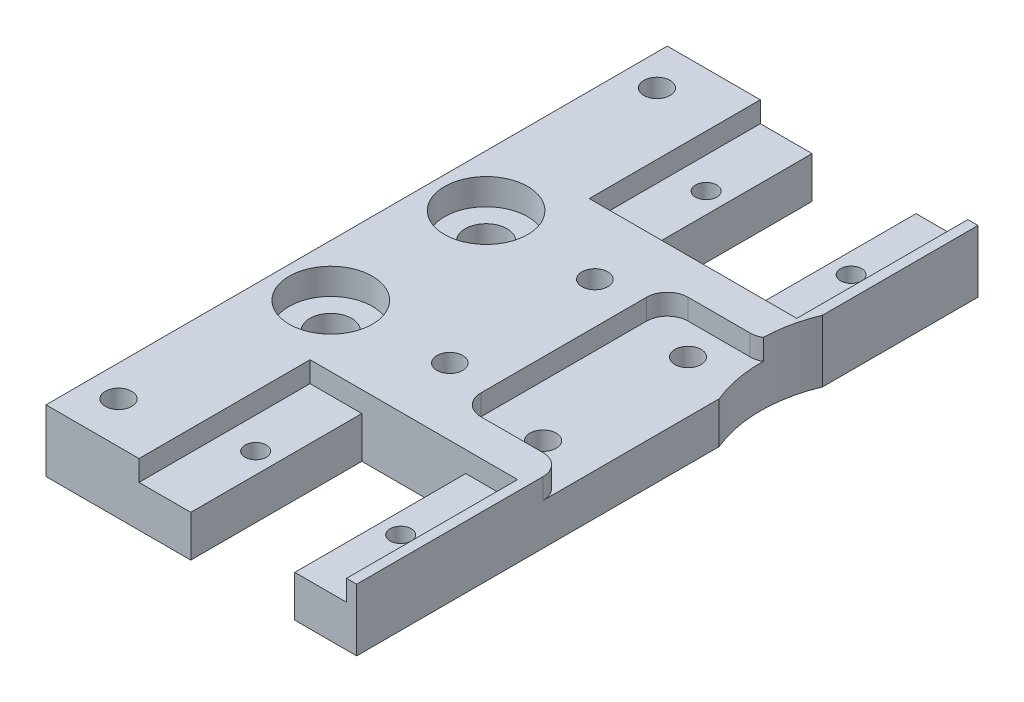
SolidWorks part; units mm, degrees
ref_plane "前视基准面" through (0, 0, 0) normal (0, 0, 1) x (1, 0, 0)
ref_plane "上视基准面" through (0, 0, 0) normal (0, 1, 0) x (1, 0, 0)
ref_plane "右视基准面" through (0, 0, 0) normal (1, 0, 0) x (0, 0, -1)
sketch "草图1" plane through (0, 0, 0) normal (0, 1, 0) x (1, 0, 0)
  line L0 (-160.9101, 0) -> (0, 0) construction
  line L3 (43, 1.5) -> (58.4568, 3.5349)
  line L4 (0, 15) -> (10, 30)
  line L5 (59.9953, -9.8805) -> (31, -30)
  line L6 (10, 30) -> (31, 30)
  line L7 (0, -15) -> (10, -30)
  line L8 (43, -1.5) -> (58.4568, -3.5349)
  line L9 (43, 1.5) -> (40, 1.5)
  line L11 (40, 1.5) -> (40, -1.5)
  line L12 (0, 15) -> (0, -15)
  line L13 (40, -1.5) -> (43, -1.5)
  line L14 (36.676, 0) -> (71.1357, 0) construction
  line L15 (59.9953, 9.8805) -> (31, 30)
  line L16 (10, -30) -> (31, -30)
  arc A3 (58.4568, 3.5349) -> (59.9953, 9.8805) centre (58, 7.005) ccw
  arc A4 (58.4568, -3.5349) -> (59.9953, -9.8805) centre (58, -7.005) cw
  point P33 (40, 0)
  dimension "D2" = 3
  dimension "D3" = 3.5
  dimension "D5" = 7.5
  dimension "D6" = 15
  dimension "D7" = 10
  dimension "D8" = 40
  dimension "D10" = 60
  dimension "D11" = 21
  dimension "D12" = 21
  dimension "D1" = 3
  dimension "D4" = 3
  dimension "D9" = 30
extrude "凸台-拉伸1" add sketch "草图1" along normal blind 2
sketch "草图2" plane through (0, 0, 0) normal (0, -1, 0) x (1, 0, 0)
  line L0 (15, 37.5) -> (15, -37.5)
  line L1 (10, -30) -> (0, -15) construction
  line L12 (10, 30) -> (0, 15)
  line L13 (0, 15) -> (0, -15)
  line L14 (0, -15) -> (10, -30)
  line L15 (31, -30) -> (59.9953, -9.8805)
  line L16 (58.4568, -3.5349) -> (43, -1.5)
  line L17 (43, -1.5) -> (40, -1.5)
  line L18 (40, -1.5) -> (40, 1.5)
  line L19 (40, 1.5) -> (43, 1.5)
  line L20 (43, 1.5) -> (58.4568, 3.5349)
  line L21 (59.9953, 9.8805) -> (31, 30)
  line L22 (10, 30) -> (0, 15)
  line L23 (0, 15) -> (0, -15)
  line L24 (0, -15) -> (10, -30)
  line L25 (31, -30) -> (59.9953, -9.8805)
  line L26 (58.4568, -3.5349) -> (43, -1.5)
  line L27 (43, -1.5) -> (40, -1.5)
  line L28 (40, -1.5) -> (40, 1.5)
  line L29 (40, 1.5) -> (43, 1.5)
  line L30 (43, 1.5) -> (58.4568, 3.5349)
  line L31 (59.9953, 9.8805) -> (31, 30)
  line L34 (31, 30) -> (10, 30)
  line L35 (31, 30) -> (10, 30)
  line L36 (10, -30) -> (31, -30)
  line L37 (10, -30) -> (31, -30)
  arc A6 (59.9953, -9.8805) -> (58.4568, -3.5349) centre (58, -7.005) ccw
  arc A7 (58.4568, 3.5349) -> (59.9953, 9.8805) centre (58, 7.005) ccw
  arc A10 (59.9953, -9.8805) -> (58.4568, -3.5349) centre (58, -7.005) ccw
  arc A11 (58.4568, 3.5349) -> (59.9953, 9.8805) centre (58, 7.005) ccw
  line M17 (10, 30) -> (0, 15)
  line M18 (0, 15) -> (0, -15)
  line M19 (0, -15) -> (10, -30)
  dimension "D2" = 15
  dimension "D1" = 0
extrude "凸台-拉伸2" add sketch "草图2" along normal blind 3 contours L0 M17 M18 M19 region at (8.3333, 0, 0)
sketch "草图3" plane through (0, 0, 0) normal (0, -1, 0) x (1, 0, 0)
  line L3 (31, -30) -> (31, 30)
  line L10 (15, 30) -> (15, -30)
  line L11 (31, -30) -> (59.9953, -9.8805)
  line L12 (58.4568, -3.5349) -> (43, -1.5)
  line L13 (43, -1.5) -> (40, -1.5)
  line L14 (40, -1.5) -> (40, 1.5)
  line L15 (40, 1.5) -> (43, 1.5)
  line L16 (43, 1.5) -> (58.4568, 3.5349)
  line L17 (59.9953, 9.8805) -> (31, 30)
  line L18 (15, 30) -> (15, -30)
  line L28 (31, 30) -> (15, 30)
  line L29 (31, 30) -> (15, 30)
  line L30 (15, -30) -> (31, -30)
  line L31 (15, -30) -> (31, -30)
  arc A7 (59.9953, -9.8805) -> (58.4568, -3.5349) centre (58, -7.005) ccw
  arc A8 (58.4568, 3.5349) -> (59.9953, 9.8805) centre (58, 7.005) ccw
  dimension "D2" = 0
extrude "凸台-拉伸3" add sketch "草图3" along normal blind 3
sketch "草图4" plane through (0, 2, 0) normal (0, 1, 0) x (1, 0, 0)
  line L0 (0, 0) -> (40, 0) construction
  line L1 (40, -1.5) -> (40, 1.5) construction
  line L2 (31, 30) -> (10, 30) construction
  line L7 (15, -30) -> (25, -30)
  line L8 (10, -30) -> (31, -30) construction
  line L9 (25, -30) -> (25, -13.5)
  line L10 (25, -13.5) -> (15, -13.5)
  line L11 (15, -13.5) -> (15, -30)
  line L12 (31, 30) -> (10, 30) construction
  line L13 (25, 13.5) -> (15, 13.5)
  line L14 (25, 30) -> (25, 13.5)
  line L15 (15, 30) -> (25, 30)
  line L16 (15, 13.5) -> (15, 30)
  point P14 (20.5, -30)
  point P17 (20.5, 30)
  dimension "D1" = 10
  dimension "D2" = 16.5
  dimension "D3" = 5
sketch "草图5" plane through (0, -3, 0) normal (0, -1, 0) x (1, 0, 0)
  line L6 (10, -30) -> (31, -30)
  line L7 (31, -30) -> (31, 30)
  line L8 (31, 30) -> (10, 30)
  line L9 (10, 30) -> (0, 15)
  line L10 (0, 15) -> (0, -15)
  line L11 (0, -15) -> (10, -30)
  line L12 (10, -30) -> (31, -30)
  line L13 (31, -30) -> (31, 30)
  line L14 (31, 30) -> (10, 30)
  line L15 (10, 30) -> (0, 15)
  line L16 (0, 15) -> (0, -15)
  line L17 (0, -15) -> (10, -30)
  dimension "D1" = 0
extrude "切除-拉伸1" cut sketch "草图5" against normal blind 1
extrude "切除-拉伸2" cut sketch "草图4" against normal through all
sketch "草图6" plane through (0, 2, 0) normal (0, 1, 0) x (1, 0, 0)
  line L1 (10, 30) -> (30, 30)
  line L2 (10, 30) -> (10, 13.5)
  line L3 (10, 13.5) -> (30, 13.5)
  line L4 (30, 30) -> (30, 13.5)
  line L5 (10, -30) -> (30, -30)
  line L6 (10, -30) -> (10, -13.5)
  line L7 (10, -13.5) -> (30, -13.5)
  line L8 (30, -30) -> (30, -13.5)
  dimension "D1" = 16.5
  dimension "D2" = 20
  dimension "D3" = 20
  dimension "D4" = 16.5
extrude "切除-拉伸4" cut sketch "草图6" against normal blind 2
sketch "草图7" plane through (0, 2, 0) normal (0, 1, 0) x (1, 0, 0)
  line L1 (40, 1.5) -> (43, 1.5) construction
  line L2 (43, -1.5) -> (40, -1.5) construction
  line L3 (0, 15) -> (0, -15) construction
  circle A0 centre (58, 7.005) radius 1
  circle A1 centre (58, -7.005) radius 1
  circle A2 centre (43, -6) radius 1
  circle A3 centre (43, 6) radius 1
  circle A4 centre (6, 7.5) radius 4
  circle A5 centre (6, -7.5) radius 4
  dimension "D1" = 2
  dimension "D2" = 2
  dimension "D3" = 2
  dimension "D4" = 2
  dimension "D5" = 4.5
  dimension "D6" = 4.5
  dimension "D7" = 8
  dimension "D8" = 8
  dimension "D9" = 6
  dimension "D10" = 6
  dimension "D11" = 6
  dimension "D12" = 6
extrude "切除-拉伸5" cut sketch "草图7" against normal blind 3.5
sketch "草图10" plane through (0, 0, 0) normal (0, -1, 0) x (1, 0, 0)
  circle A0 centre (43, 6) radius 4
  dimension "D1" = 8
extrude "凸台-拉伸5" add sketch "草图10" along normal blind 2
sketch "草图11" plane through (0, 2, 0) normal (0, 1, 0) x (1, 0, 0)
  circle A0 centre (43, -6) radius 3
  dimension "D1" = 6
extrude "切除-拉伸6" cut sketch "草图11" against normal blind 2.5
sketch "草图12" plane through (0, -0.5, 0) normal (0, 1, 0) x (1, 0, 0)
  circle A0 centre (43, -6) radius 1.75
  dimension "D1" = 3.5
extrude "切除-拉伸7" cut sketch "草图12" against normal blind 2.5
sketch "草图14" plane through (0, 2, 0) normal (0, 1, 0) x (1, 0, 0)
  circle A0 centre (6, 7.5) radius 1.5
  circle A1 centre (6, -7.5) radius 1.5
  dimension "D1" = 3
  dimension "D2" = 3
extrude "切除-拉伸8" cut sketch "草图14" against normal through all
sketch "草图15" plane through (0, 0, 0) normal (0, 1, 0) x (1, 0, 0)
  line L0 (15, 13.5) -> (15, 30) construction
  line L1 (25, 30) -> (25, 13.5) construction
  line L2 (25, -30) -> (25, -13.5) construction
  line L3 (15, -13.5) -> (15, -30) construction
  line L4 (10, -30) -> (15, -30) construction
  line L5 (25, -30) -> (30, -30) construction
  line L6 (30, 30) -> (25, 30) construction
  line L7 (15, 30) -> (10, 30) construction
  circle A0 centre (13, 21.75) radius 1.25
  circle A1 centre (27, 21.75) radius 1.25
  circle A2 centre (27, -21.75) radius 1.25
  circle A3 centre (13, -21.75) radius 1.25
  dimension "D1" = 2
  dimension "D2" = 2
  dimension "D3" = 2
  dimension "D4" = 2
  dimension "D5" = 2.5
  dimension "D6" = 2.5
  dimension "D7" = 2.5
  dimension "D8" = 2.5
  dimension "D9" = 8.25
  dimension "D10" = 8.25
  dimension "D11" = 8.25
  dimension "D12" = 8.25
extrude "切除-拉伸9" cut sketch "草图15" against normal blind 10
sketch "草图16" plane through (0, 2, 0) normal (0, 1, 0) x (1, 0, 0)
  line L0 (40, 0) -> (0, 0)
  line L1 (40, -1.5) -> (40, 1.5) construction
  circle A0 centre (17, 7) radius 1.25
  circle A1 centre (17, -7) radius 1.25
  circle A2 centre (37, 16) radius 1.25
  circle A3 centre (37, -16) radius 1.25
  dimension "D1" = 2.5
  dimension "D2" = 2.5
  dimension "D3" = 7
  dimension "D4" = 7
  dimension "D5" = 23
  dimension "D6" = 23
  dimension "D7" = 2.5
  dimension "D8" = 2.5
  dimension "D9" = 16
  dimension "D10" = 3
  dimension "D11" = 16
  dimension "D12" = 3
extrude "切除-拉伸10" cut sketch "草图16" against normal blind 10 contours A1 | A0 | A2 | A3 region at (17, 2, -7) region at (17, 2, 7) region at (37, 2, -16) region at (37, 2, 16)
sketch "草图17" plane through (0, -1.5, 0) normal (0, 1, 0) x (1, 0, 0)
  circle A0 centre (6, 7.5) radius 4.5
  circle A1 centre (6, -7.5) radius 4.5
  circle A2 centre (6, 12) radius 0.8
  dimension "D1" = 9
  dimension "D2" = 9
  dimension "D3" = 1.6
sketch "草图18" plane through (0, -2, 0) normal (0, -1, 0) x (1, 0, 0)
  line L0 (0, 15) -> (10.5, 15)
  line L1 (10.5, 15) -> (10.5, -15)
  line L2 (10.5, -15) -> (0, -15)
  line L3 (0, 15) -> (0, -15) construction
  line L4 (0, -15) -> (0, 15)
  circle A0 centre (6, -7.5) radius 4.5 construction
  circle A1 centre (6, 7.5) radius 1.5 construction
  circle A2 centre (6, 7.5) radius 1.5
  circle A3 centre (6, -7.5) radius 1.5 construction
  circle A4 centre (6, -7.5) radius 1.5
extrude "凸台-拉伸6" add sketch "草图18" along normal blind 2
sketch "草图19" plane through (0, 2, 0) normal (0, 1, 0) x (1, 0, 0)
  circle A0 centre (6, 12) radius 1.75
  circle A1 centre (6, 3) radius 1.75
  circle A2 centre (6, 7.5) radius 4.5 construction
  dimension "D1" = 3.5
  dimension "D2" = 3.5
extrude "切除-拉伸11" cut sketch "草图19" against normal offset from surface (5 mm away) 1 up to face at (5.25, -4, 0)
sketch "草图20" plane through (0, -3, 0) normal (0, 1, 0) x (1, 0, 0)
  circle A0 centre (6, 12) radius 0.9
  circle A1 centre (6, 3) radius 0.9
  dimension "D1" = 1.8
  dimension "D2" = 1.8
extrude "切除-拉伸12" cut sketch "草图20" against normal through all
sketch "草图22" plane through (0, 2, 0) normal (0, 1, 0) x (1, 0, 0)
  circle A0 centre (6, -3) radius 1.75
  circle A1 centre (6, -7.5) radius 4.5 construction
  circle A2 centre (6, -12) radius 1.75
  dimension "D1" = 3.5
  dimension "D2" = 3.5
extrude "切除-拉伸13" cut sketch "草图22" against normal offset from surface (5 mm away) 1 up to face at (6, -4, -11.1)
sketch "草图23" plane through (0, -3, 0) normal (0, 1, 0) x (1, 0, 0)
  circle A0 centre (6, -3) radius 0.9
  circle A1 centre (6, -12) radius 0.9
  dimension "D1" = 1.8
  dimension "D2" = 1.8
extrude "切除-拉伸14" cut sketch "草图23" against normal through all
fillet "圆角1" radius 2 1 edges at (10.5, -3, 15)
fillet "圆角2" radius 2 1 edges at (10.5, -3, -15)
sketch "草图24" plane through (0, 2, 0) normal (0, 1, 0) x (1, 0, 0)
  line L0 (10, 30) -> (0, 30)
  line L1 (0, 30) -> (0, 15)
  line L2 (0, 15) -> (10, 30)
  line L3 (0, -15) -> (0, -30)
  line L4 (0, -30) -> (10, -30)
  line L5 (10, -30) -> (0, -15)
extrude "凸台-拉伸7" add sketch "草图24" against normal up to surface (4 mm away) up to face at (13, -2, -20.5)
sketch "草图25" plane through (0, 2, 0) normal (0, 1, 0) x (1, 0, 0)
  line L0 (0, 30) -> (0, -30) construction
  line L1 (10, 30) -> (0, 30) construction
  line L2 (0, -30) -> (10, -30) construction
  circle A0 centre (4, 26) radius 1.25
  circle A1 centre (4, -26) radius 1.25
  dimension "D1" = 4
  dimension "D2" = 4
  dimension "D3" = 4
  dimension "D4" = 2.5
  dimension "D5" = 4
  dimension "D6" = 2.5
extrude "切除-拉伸15" cut sketch "草图25" against normal blind 10
sketch "草图26" plane through (0, 2, 0) normal (0, 1, 0) x (1, 0, 0)
  line L21 (9.98, 30) -> (30.02, 30)
  line L24 (30.02, 13.48) -> (30.02, 30)
  line L25 (9.98, 13.48) -> (30.02, 13.48)
  line L26 (9.98, 30) -> (9.98, 13.48)
  line L27 (30.02, 13.48) -> (30.02, 30)
  line L28 (9.98, 13.48) -> (30.02, 13.48)
  line L29 (9.98, 30) -> (9.98, 13.48)
  line L34 (9.98, -30) -> (30.02, -30)
  line L37 (30.02, -30) -> (30.02, -13.48)
  line L38 (30.02, -13.48) -> (9.98, -13.48)
  line L39 (9.98, -13.48) -> (9.98, -30)
  line L40 (30.02, -30) -> (30.02, -13.48)
  line L41 (30.02, -13.48) -> (9.98, -13.48)
  line L42 (9.98, -13.48) -> (9.98, -30)
  dimension "D1" = 0.02
  dimension "D2" = 0.02
extrude "切除-拉伸16" cut sketch "草图26" against normal up to surface (2 mm away) up to face at (27, 0, 23)
sketch "草图27" plane through (0, 0, 0) normal (0, 1, 0) x (1, 0, 0)
  line L0 (9.98, 13.48) -> (30.02, 13.48) construction
  line L1 (14.98, 13.48) -> (25.02, 13.48)
  line L2 (30.02, -13.48) -> (9.98, -13.48) construction
  line L3 (25.02, -13.48) -> (14.98, -13.48)
  line L9 (14.98, -13.5) -> (14.98, -30)
  line L10 (14.98, -13.48) -> (14.98, -30)
  line L11 (14.98, -30) -> (25.02, -30)
  line L12 (25.02, -30) -> (25.02, -13.5)
  line L13 (25.02, -30) -> (25.02, -13.48)
  line L18 (14.98, 13.5) -> (14.98, 30)
  line L19 (14.98, 13.48) -> (14.98, 30)
  line L20 (14.98, 30) -> (25.02, 30)
  line L21 (25.02, 30) -> (25.02, 13.5)
  line L22 (25.02, 30) -> (25.02, 13.48)
  dimension "D1" = 0.02
  dimension "D2" = 0.02
  dimension "D4" = 0.02
  dimension "D5" = 0.02
extrude "切除-拉伸17" cut sketch "草图27" against normal up to surface (2 mm away) up to face at (4, -2, -24.75)
sketch "草图28" plane through (0, 2, 0) normal (0, 1, 0) x (1, 0, 0)
  circle A5 centre (43, 6) radius 1.02
  circle A6 centre (43, 6) radius 1.02
  circle A13 centre (58, 7.005) radius 1.02
  circle A14 centre (58, 7.005) radius 1.02
  circle A16 centre (58, -7.005) radius 1.02
  circle A17 centre (58, -7.005) radius 1.02
  circle A19 centre (6, 12) radius 0.92
  circle A20 centre (6, 12) radius 0.92
  circle A22 centre (6, 3) radius 0.92
  circle A23 centre (6, 3) radius 0.92
  circle A25 centre (6, -3) radius 0.92
  circle A26 centre (6, -3) radius 0.92
  circle A28 centre (6, -12) radius 0.92
  circle A29 centre (6, -12) radius 0.92
  circle A31 centre (4, 26) radius 1.27
  circle A32 centre (4, 26) radius 1.27
  circle A34 centre (4, -26) radius 1.27
  circle A35 centre (4, -26) radius 1.27
  dimension "D1" = 0.02
  dimension "D2" = 0.02
  dimension "D3" = 0.02
  dimension "D4" = 0.02
  dimension "D5" = 0.02
  dimension "D6" = 0.02
  dimension "D7" = 0.02
  dimension "D8" = 0.02
  dimension "D9" = 0.02
extrude "切除-拉伸18" cut sketch "草图28" against normal through all both and the other way through all
sketch "草图29" plane through (0, 0, 0) normal (0, 1, 0) x (1, 0, 0)
  point P0 (13, 21.75)
  point P1 (27, 21.75)
  point P3 (27, -21.75)
  point P5 (13, -21.75)
sketch "草图30" plane through (0, 0, 0) normal (0, 1, 0) x (1, 0, 0)
  circle A0 centre (13, 21.75) radius 1.5751
  circle A1 centre (27, 21.75) radius 1.9311
  circle A2 centre (27, -21.75) radius 1.7161
  circle A3 centre (13, -21.75) radius 1.8166
extrude "凸台-拉伸8" add sketch "草图30" against normal up to surface (2 mm away) up to face at (4, -2, 27.27)
hole_wizard "M2.5 螺纹孔1" positions "草图31" profile "草图32" tap size "M2.5" standard "GB" end condition through all
sketch "草图31" plane through (0, 0, 0) normal (0, 1, 0) x (1, 0, 0)
  point P0 (13, 21.75)
  point P3 (27, 21.75)
  point P6 (27, -21.75)
  point P9 (13, -21.75)
sketch "草图32" plane through (13, 0, -21.75) normal (1, 0, 0) x (0, 0, 1)
  line L0 (0, 0) -> (0, 4)
  line L1 (0, 4) -> (1.025, 4)
  line L2 (1.025, 4) -> (1.025, 0)
  line L5 (1.025, 0) -> (0, 0)
  line L11 (0, -6.35) -> (0, 107.95) construction
  dimension "通孔螺纹孔钻头直径" = 2.05
  dimension "通孔螺纹孔钻头深度" = 4
sketch "草图33" plane through (0, 2, 0) normal (0, 1, 0) x (1, 0, 0)
  circle A0 centre (43, -6) radius 3.02
  circle A1 centre (43, -6) radius 3 construction
  dimension "D1" = 0.02
extrude "切除-拉伸19" cut sketch "草图33" against normal blind 2.53
sketch "草图35" plane through (0, -1.5, 0) normal (0, 1, 0) x (1, 0, 0)
  circle A0 centre (6, 7.5) radius 1.5 construction
  circle A1 centre (6, 7.5) radius 1.5
  circle A2 centre (6, -7.5) radius 1.5 construction
  circle A3 centre (6, -7.5) radius 1.5
  arc A4 (4.4501, -3.8125) -> (7.5499, -3.8125) centre (6, -3) ccw
  arc A5 (4.4501, -3.8125) -> (4.4501, -11.1875) centre (6, -7.5) ccw
  arc A6 (7.5499, -11.1875) -> (4.4501, -11.1875) centre (6, -12) ccw
  arc A7 (7.5499, -11.1875) -> (7.5499, -3.8125) centre (6, -7.5) ccw
  arc A8 (4.4501, -3.8125) -> (7.5499, -3.8125) centre (6, -3) ccw
  arc A9 (4.4501, -3.8125) -> (4.4501, -11.1875) centre (6, -7.5) ccw
  arc A10 (7.5499, -11.1875) -> (4.4501, -11.1875) centre (6, -12) ccw
  arc A11 (7.5499, -11.1875) -> (7.5499, -3.8125) centre (6, -7.5) ccw
  arc A12 (4.4501, 11.1875) -> (7.5499, 11.1875) centre (6, 12) ccw
  arc A13 (4.4501, 11.1875) -> (4.4501, 3.8125) centre (6, 7.5) ccw
  arc A14 (7.5499, 3.8125) -> (4.4501, 3.8125) centre (6, 3) ccw
  arc A15 (7.5499, 3.8125) -> (7.5499, 11.1875) centre (6, 7.5) ccw
  arc A16 (4.4501, 11.1875) -> (7.5499, 11.1875) centre (6, 12) ccw
  arc A17 (4.4501, 11.1875) -> (4.4501, 3.8125) centre (6, 7.5) ccw
  arc A18 (7.5499, 3.8125) -> (4.4501, 3.8125) centre (6, 3) ccw
  arc A19 (7.5499, 3.8125) -> (7.5499, 11.1875) centre (6, 7.5) ccw
  arc M9 (7.5499, -3.8125) -> (4.4501, -3.8125) centre (6, -3) cw
  arc M10 (4.4501, -3.8125) -> (4.4501, -11.1875) centre (6, -7.5) ccw
  arc M11 (4.4501, -11.1875) -> (7.5499, -11.1875) centre (6, -12) cw
  arc M12 (7.5499, -11.1875) -> (7.5499, -3.8125) centre (6, -7.5) ccw
  circle M13 centre (6, -7.5) radius 1.5
  dimension "D1" = 0
  dimension "D2" = 0
extrude "凸台-拉伸9" add sketch "草图35" along normal up to surface (3.5 mm away) contours A18 A19 A16 A17 A1 | M12 M9 M10 M11 M13 region at (6, -1.5, 4.8588) region at (6, -1.5, -10.1412) up to face at (43, 2, 9.02)
sketch "草图36" plane through (0, 2, 0) normal (0, 1, 0) x (1, 0, 0)
  circle A0 centre (6, 7.5) radius 4.02
  circle A1 centre (6, -7.5) radius 4.02
  dimension "D1" = 8.04
  dimension "D2" = 8.04
extrude "切除-拉伸21" cut sketch "草图36" against normal blind 2.53
sketch "草图37" plane through (0, -3, 0) normal (0, 1, 0) x (1, 0, 0)
  circle A0 centre (6, -12) radius 0.92 construction
  circle A1 centre (6, 12) radius 1.75
  circle A2 centre (6, 12) radius 1.75
  circle A3 centre (6, 3) radius 1.75
  circle A4 centre (6, 3) radius 1.75
  circle A5 centre (6, -3) radius 1.75
  circle A6 centre (6, -3) radius 1.75
  circle A7 centre (6, -12) radius 1.75
  circle A8 centre (6, -12) radius 1.75
  circle A9 centre (6, -12) radius 0.92
  circle A10 centre (6, -3) radius 0.92 construction
  circle A11 centre (6, -3) radius 0.92
  circle A12 centre (6, 3) radius 0.92 construction
  circle A13 centre (6, 3) radius 0.92
  circle A14 centre (6, 12) radius 0.92 construction
  circle A15 centre (6, 12) radius 0.92
  circle M6 centre (6, 12) radius 0.92
  circle M7 centre (6, 12) radius 1.75
  dimension "D1" = 0
  dimension "D2" = 0
  dimension "D3" = 0
  dimension "D4" = 0
extrude "凸台-拉伸10" add sketch "草图37" along normal offset from surface (0.47 mm away) 2 contours M7 M6 | A4 A13 | A6 A11 | A8 A9 region at (4.2995, -3, -12) region at (4.2995, -3, -3) region at (4.2995, -3, 3) region at (4.2995, -3, 12) up to face at (6, -0.53, 7.5)
sketch "草图38" plane through (0, -0.53, 0) normal (0, 1, 0) x (1, 0, 0)
  circle A0 centre (6, 7.5) radius 2.02
  circle A1 centre (6, -7.5) radius 2.02
  dimension "D1" = 4.04
  dimension "D2" = 4.04
extrude "切除-拉伸22" cut sketch "草图38" against normal through all both and the other way through all
sketch "草图39" plane through (0, 0, 0) normal (0, -1, 0) x (1, 0, 0)
  line L1 (31, -30) -> (63.4857, -30)
  line L2 (31, -30) -> (31, 31.8311)
  line L3 (31, 31.8311) -> (63.4857, 31.8311)
  line L4 (63.4857, -30) -> (63.4857, 31.8311)
extrude "切除-拉伸23" cut sketch "草图39" against normal through all both and the other way through all
sketch "草图40" plane through (31, 0, 0) normal (1, 0, 0) x (0, 0, -1)
  line L0 (-30, 2) -> (30, 2) construction
  line L1 (-10, 0) -> (10, 0)
  line L2 (-10, 0) -> (-10, 4)
  line L3 (-10, 4) -> (10, 4)
  line L4 (10, 0) -> (10, 4)
  line L5 (-10, 0) -> (10, 4) construction
  line L6 (-10, 4) -> (10, 0) construction
  point P0 (0, 2)
  dimension "D1" = 20
  dimension "D2" = 4
extrude "切除-拉伸24" cut sketch "草图40" against normal blind 10 and the other way through all
sketch "草图41" plane through (0, -2, 0) normal (0, -1, 0) x (1, 0, 0)
  line L16 (31, 30) -> (25.02, 30)
  line L17 (25.02, 30) -> (25.02, 13.48)
  line L18 (25.02, 13.48) -> (14.98, 13.48)
  line L19 (14.98, 13.48) -> (14.98, 30)
  line L20 (14.98, 30) -> (0, 30)
  line L21 (0, 30) -> (0, 15)
  line L22 (0, 15) -> (8.5, 15)
  line L23 (10.5, 13) -> (10.5, -13)
  line L24 (8.5, -15) -> (0, -15)
  line L25 (0, -15) -> (0, -30)
  line L26 (0, -30) -> (14.98, -30)
  line L27 (14.98, -30) -> (14.98, -13.48)
  line L28 (14.98, -13.48) -> (25.02, -13.48)
  line L29 (25.02, -13.48) -> (25.02, -30)
  line L30 (25.02, -30) -> (31, -30)
  line L31 (31, -30) -> (31, 30)
  line L32 (31, 30) -> (25.02, 30)
  line L33 (25.02, 30) -> (25.02, 13.48)
  line L34 (25.02, 13.48) -> (14.98, 13.48)
  line L35 (14.98, 13.48) -> (14.98, 30)
  line L36 (14.98, 30) -> (0, 30)
  line L37 (0, 30) -> (0, 15)
  line L38 (0, 15) -> (8.5, 15)
  line L39 (10.5, 13) -> (10.5, -13)
  line L40 (8.5, -15) -> (0, -15)
  line L41 (0, -15) -> (0, -30)
  line L42 (0, -30) -> (14.98, -30)
  line L43 (14.98, -30) -> (14.98, -13.48)
  line L44 (14.98, -13.48) -> (25.02, -13.48)
  line L45 (25.02, -13.48) -> (25.02, -30)
  line L46 (25.02, -30) -> (31, -30)
  line L47 (31, -30) -> (31, 30)
  circle A0 centre (4, -26) radius 1.27 construction
  circle A1 centre (13, -21.75) radius 1.025 construction
  arc A2 (10.5, 13) -> (8.5, 15) centre (8.5, 13) ccw
  arc A3 (8.5, -15) -> (10.5, -13) centre (8.5, -13) ccw
  arc A4 (10.5, 13) -> (8.5, 15) centre (8.5, 13) ccw
  arc A5 (8.5, -15) -> (10.5, -13) centre (8.5, -13) ccw
  circle A6 centre (27, -21.75) radius 1.025 construction
  circle A7 centre (17, -7) radius 1.25 construction
  circle A8 centre (17, 7) radius 1.25 construction
  circle A9 centre (27, 21.75) radius 1.025 construction
  circle A10 centre (13, 21.75) radius 1.025 construction
  circle A11 centre (4, 26) radius 1.27 construction
  circle A12 centre (4, -26) radius 1.27
  circle A13 centre (13, -21.75) radius 1.025
  circle A14 centre (27, -21.75) radius 1.025
  circle A15 centre (17, -7) radius 1.25
  circle A16 centre (17, 7) radius 1.25
  circle A17 centre (27, 21.75) radius 1.025
  circle A18 centre (13, 21.75) radius 1.025
  circle A19 centre (4, 26) radius 1.27
  dimension "D1" = 0
extrude "凸台-拉伸11" add sketch "草图41" along normal up to surface (2 mm away) up to face at (6, -4, -5.48)
fillet "圆角4" radius 2 4 edges at (31, 1, 10) (31, 1, -10) (21, 1, -10) (21, 1, 10)
sketch "草图42" plane through (0, 0, 0) normal (0, 1, 0) x (1, 0, 0)
  line L0 (29, 10) -> (23, 10) construction
  line L1 (29, -10) -> (23, -10) construction
  line L2 (21, -8) -> (21, 8) construction
  circle A0 centre (26, 7) radius 1.27
  circle A1 centre (26, -7) radius 1.27
  dimension "D1" = 2.54
  dimension "D2" = 2.54
  dimension "D3" = 3
  dimension "D4" = 3
  dimension "D5" = 5
extrude "切除-拉伸25" cut sketch "草图42" against normal blind 10
sketch "草图43" plane through (0, 2, 0) normal (0, 1, 0) x (1, 0, 0)
  line L0 (9.98, 30) -> (0, 30) construction
  line L1 (0, -30) -> (1, -30)
  line L2 (0, -30) -> (0, 30)
  line L3 (0, 30) -> (1, 30)
  line L4 (1, -30) -> (1, 30)
  dimension "D1" = 1
extrude "切除-拉伸26" cut sketch "草图43" against normal blind 10
sketch "草图44" plane through (0, -4, 0) normal (0, -1, 0) x (1, 0, 0)
  circle A0 centre (43, -10) radius 13
  dimension "D1" = 26
extrude "切除-拉伸27" cut sketch "草图44" against normal blind 10
sketch "草图45" plane through (0, -2.53, 0) normal (0, 1, 0) x (1, 0, 0)
  circle A0 centre (6, -3) radius 1.75 construction
  circle A1 centre (6, 12) radius 1.75
  circle A2 centre (6, 12) radius 1.75
  circle A3 centre (6, 3) radius 1.75
  circle A4 centre (6, 3) radius 1.75
  circle A5 centre (6, -12) radius 1.75 construction
  circle A6 centre (6, -3) radius 1.75
  circle A7 centre (6, -12) radius 1.75
  dimension "D1" = 0
  dimension "D2" = 0
extrude "凸台-拉伸12" add sketch "草图45" along normal up to surface (4.53 mm away) from surface up to face at (17, 2, 8.25) starting at face at (26, -4, -5.73)
sketch "草图46" plane through (0, 2, 0) normal (0, 1, 0) x (1, 0, 0)
  circle A0 centre (6, 7.5) radius 4.02
  circle A1 centre (6, -7.5) radius 4.02
extrude "切除-拉伸28" cut sketch "草图46" against normal up to surface (2.53 mm away) up to face at (6, -0.53, -5.48)
